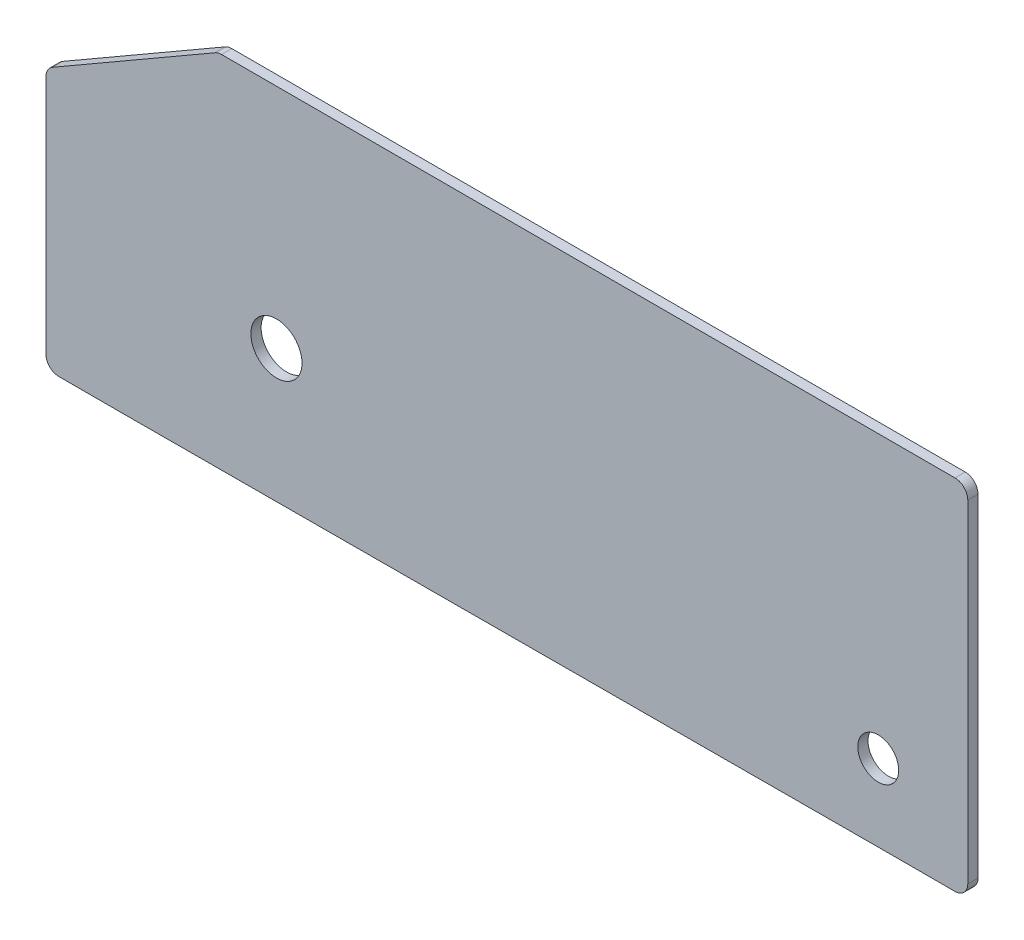
SolidWorks part; units mm, degrees
ref_plane "Front Plane" through (0, 0, 0) normal (0, 0, 1) x (1, 0, 0)
ref_plane "Top Plane" through (0, 0, 0) normal (0, 1, 0) x (1, 0, 0)
ref_plane "Right Plane" through (0, 0, 0) normal (1, 0, 0) x (0, 0, -1)
sketch "Sketch1" plane through (0, 0, 0) normal (0, 0, 1) x (1, 0, 0)
  line L0 (16.6619, 10.0158) -> (4.1619, 10.0158)
  line L1 (19.1619, 77.5158) -> (19.1619, 12.5158)
  line L2 (-126.7041, 80.0158) -> (16.6619, 80.0158)
  line L3 (-146.015, 9.5932) -> (-158.515, 9.5932)
  line L4 (-127.9541, 79.6809) -> (-159.765, 61.3149)
  line L5 (-161.015, 59.1498) -> (-161.015, 12.0932)
  line L6 (-146.015, 9.5932) -> (4.1619, 10.0158)
  arc A0 (16.6619, 10.0158) -> (19.1619, 12.5158) centre (16.6619, 12.5158) ccw
  arc A1 (19.1619, 77.5158) -> (16.6619, 80.0158) centre (16.6619, 77.5158) ccw
  arc A2 (-126.7041, 80.0158) -> (-127.9541, 79.6809) centre (-126.7041, 77.5158) ccw
  arc A3 (-161.015, 12.0932) -> (-158.515, 9.5932) centre (-158.515, 12.0932) ccw
  arc A4 (-159.765, 61.3149) -> (-161.015, 59.1498) centre (-158.515, 59.1498) ccw
base flange "Base-Flange1" sketch "Sketch1" thickness 2 reverse thickness direction no parameters "D1"=0.5
sketch "Sketch2" plane through (0, 0, -2) normal (0, 0, -1) x (-1, 0, 0)
  circle A0 centre (115.9708, 35.6215) radius 5
  dimension "D1" = 10
extrude "Cut-Extrude1" cut sketch "Sketch2" against normal blind 10 normal cut yes
sketch "Sketch4" plane through (0, 0, 0) normal (0, 0, 1) x (1, 0, 0)
  circle A0 centre (1.6619, 25.0158) radius 4
  dimension "D3" = 8
extrude "Cut-Extrude3" cut sketch "Sketch4" against normal blind 10 normal cut yes
sketch "Bend-Lines1" [suppressed] plane through (0, 0, 0) normal (0, 1, 0) x (1, 0, 0)
sketch "Bounding-Box1" [suppressed] plane through (0, 0, 0) normal (0, 1, 0) x (1, 0, 0)
sheet metal parameters "Sheet-Metal1" thickness 2 parameters "D1"=0.5
flat pattern "Flat-Pattern1" [suppressed]
sketch "Bend-Lines2" plane through (0, 0, 0) normal (0, 1, 0) x (1, 0, 0)
sketch3d "Bounding-Box2" [suppressed]
  line L0 (177.6769, -2.9226, 0) -> (-2.5, -2.9226, 0) construction
  line L1 (177.6769, 67.5, 0) -> (-2.5, 67.5, 0) construction
  line L2 (177.6769, -2.9226, 0) -> (177.6769, 67.5, 0) construction
  line L3 (-2.5, -2.9226, 0) -> (-2.5, 67.5, 0) construction
sheet metal parameters "Sheet-Metal2" thickness 2 parameters "D1"=0.5
flat pattern "Flat-Pattern1"
sketch "Bend-Lines2" plane through (0, 0, 0) normal (0, 1, 0) x (1, 0, 0)
sketch3d "Bounding-Box2" [suppressed]
  line L0 (-177.6769, -2.9226, 0) -> (2.5, -2.9226, 0) construction
  line L1 (-177.6769, 67.5, 0) -> (2.5, 67.5, 0) construction
  line L2 (-177.6769, -2.9226, 0) -> (-177.6769, 67.5, 0) construction
  line L3 (2.5, -2.9226, 0) -> (2.5, 67.5, 0) construction
sheet metal parameters "Sheet-Metal4" thickness 2 parameters "D1"=0.5
flat pattern "Flat-Pattern1"
sketch "Bend-Lines2" plane through (0, 0, 0) normal (0, 1, 0) x (1, 0, 0)
sketch3d "Bounding-Box2" [suppressed]
  line L0 (-177.6769, -2.9226, 0) -> (2.5, -2.9226, 0) construction
  line L1 (-177.6769, 67.5, 0) -> (2.5, 67.5, 0) construction
  line L2 (-177.6769, -2.9226, 0) -> (-177.6769, 67.5, 0) construction
  line L3 (2.5, -2.9226, 0) -> (2.5, 67.5, 0) construction
